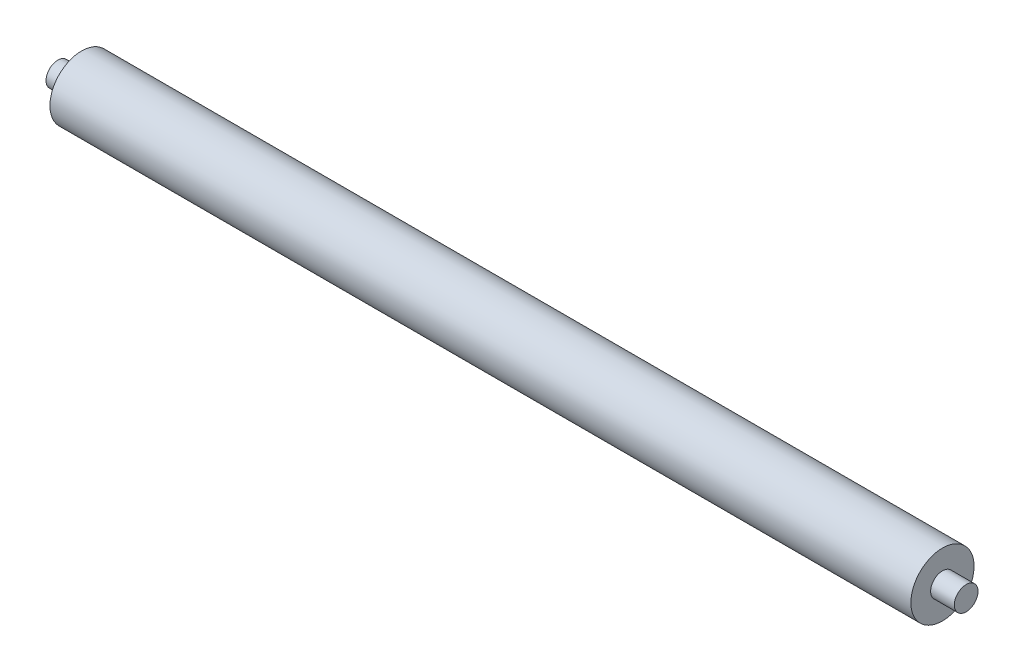
SolidWorks part; units mm, degrees
ref_plane "Plan de face" through (0, 0, 0) normal (0, 0, 1) x (1, 0, 0)
ref_plane "Plan de dessus" through (0, 0, 0) normal (0, 1, 0) x (1, 0, 0)
ref_plane "Plan de droite" through (0, 0, 0) normal (1, 0, 0) x (0, 0, -1)
sketch "Esquisse1" plane through (0, 0, 0) normal (0, 0, 1) x (1, 0, 0)
  line L0 (0, 0) -> (115, 0)
  line L1 (115, 0) -> (115, 1.5)
  line L2 (115, 1.5) -> (112, 1.5)
  line L3 (112, 1.5) -> (112, 4)
  line L4 (112, 4) -> (3, 4)
  line L5 (3, 4) -> (3, 1.5)
  line L6 (3, 1.5) -> (0, 1.5)
  line L7 (0, 1.5) -> (0, 0)
  dimension "D1" = 1.5
  dimension "D2" = 4
  dimension "D3" = 3
  dimension "D4" = 115
revolve "Révolution1" add sketch "Esquisse1" angle 360 about L0
